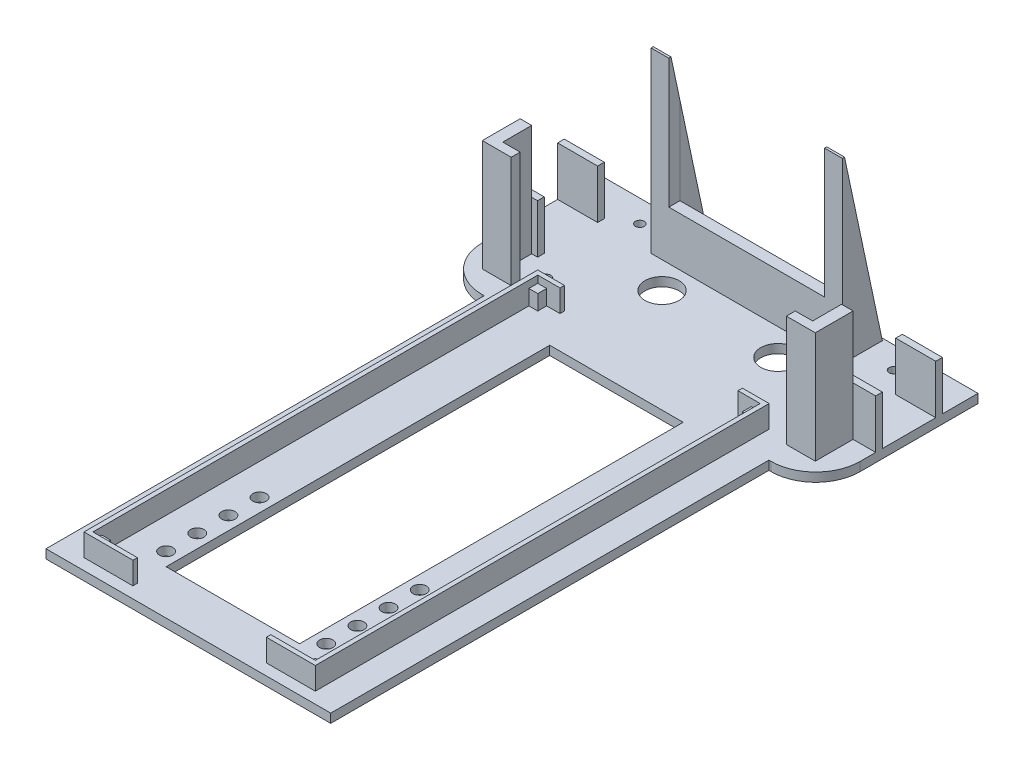
SolidWorks part; units mm, degrees
ref_plane "Front Plane" through (0, 0, 0) normal (0, 0, 1) x (1, 0, 0)
ref_plane "Top Plane" through (0, 0, 0) normal (0, 1, 0) x (1, 0, 0)
ref_plane "Right Plane" through (0, 0, 0) normal (1, 0, 0) x (0, 0, -1)
sketch "base" plane through (0, 0, 0) normal (0, 1, 0) x (1, 0, 0)
  line L1 (-42.5, 50) -> (42.5, 50)
  line L2 (-42.5, 50) -> (-42.5, -50)
  line L3 (-42.5, -50) -> (42.5, -50)
  line L4 (42.5, 50) -> (42.5, -50)
  line L5 (-42.5, 50) -> (42.5, -50) construction
  line L6 (-42.5, -50) -> (42.5, 50) construction
  point P0 (0, 0)
extrude "Boss-Extrude2" add sketch "base" along normal blind 2
sketch "Sketch3" plane through (0, 2, 0) normal (0, 1, 0) x (1, 0, 0)
  line L0 (42.5, 50) -> (-42.5, 50) construction
  line L9 (42.5, 40.5) -> (33.5, 40.5)
  line L10 (42.5, 40.5) -> (42.5, 42)
  line L11 (42.5, 42) -> (33.5, 42)
  line L12 (33.5, 40.5) -> (33.5, 42)
  line L13 (42.5, 28.5) -> (33.5, 28.5)
  line L14 (42.5, 28.5) -> (42.5, 27)
  line L15 (42.5, 27) -> (33.5, 27)
  line L16 (33.5, 28.5) -> (33.5, 27)
  line L17 (0, 50) -> (0, 24.8755)
  line L18 (-42.5, 42) -> (-33.5, 42)
  line L19 (-33.5, 40.5) -> (-33.5, 42)
  line L20 (-42.5, 40.5) -> (-33.5, 40.5)
  line L21 (-42.5, 40.5) -> (-42.5, 42)
  line L22 (-42.5, 27) -> (-33.5, 27)
  line L23 (-33.5, 28.5) -> (-33.5, 27)
  line L24 (-42.5, 28.5) -> (-33.5, 28.5)
  line L25 (-42.5, 28.5) -> (-42.5, 27)
  line L27 (-21.5, 40.5) -> (21.5, 40.5)
  line L28 (-21.5, 40.5) -> (-21.5, 43)
  line L29 (-21.5, 43) -> (21.5, 43)
  line L30 (21.5, 40.5) -> (21.5, 43)
  point P26 (21.5, 41.75)
  dimension "D1" = 9.5
  dimension "D2" = 9
  dimension "D3" = 12
  dimension "D4" = 12
  dimension "D5" = 12
  dimension "D7" = 8
  dimension "D8" = 7
  dimension "D9" = 9.5
  dimension "D11" = 1.5
extrude "Boss-Extrude4" add sketch "Sketch3" along normal blind 11 contours L18 L19 L20 L21 | L22 L23 L24 L25 | L28 L27 L30 L29 | L10 L9 L12 L11 | L14 L13 L16 L15
sketch "Sketch13" plane through (0, 2, 0) normal (0, 1, 0) x (1, 0, 0)
  line L0 (33.5, 40.5) -> (33.5, 42) construction
  line L1 (42.5, 42) -> (33.5, 42) construction
  line L2 (42.5, 28.5) -> (42.5, 40.5) construction
  line L3 (42.5, 34.5) -> (-42.5, 34.5)
  line L4 (-42.5, 40.5) -> (-42.5, 28.5) construction
  line L5 (-42.5, 34.5) -> (42.5, 34.5)
  line L6 (0, 50) -> (0, -50)
  line L7 (-42.5, -50) -> (42.5, -50) construction
  line L9 (-15, -50) -> (15, -50)
  line L10 (-15, -50) -> (-15, 11.2308)
  line L11 (-15, 11.2308) -> (15, 11.2308)
  line L12 (15, -50) -> (15, 11.2308)
  circle A0 centre (28.5, 45) radius 1
  circle A1 centre (28.5, 24) radius 1
  circle A2 centre (-28.5, 24) radius 1
  circle A3 centre (-28.5, 45) radius 1
  circle A4 centre (13.025, 34.5) radius 3.8478
  circle A5 centre (-13.025, 34.5) radius 3.8478
  line M29 (-42.5, -50) -> (42.5, -50)
  dimension "D1" = 2
  dimension "D4" = 30
  dimension "D2" = 5
  dimension "D3" = 3
  dimension "D5" = 15
extrude "Cut-Extrude2" cut sketch "Sketch13" against normal through all contours A5 L3 | A5 L3 | L3 A4 | L3 A4 | L11 L10 L6 M29 | L12 L11 L6 M29 | A0 | A1 | A2 | A3 region at (13.025, 2, -32.8669) region at (13.025, 2, -36.1331) region at (7.5, 2, 19.3846) region at (-7.5, 2, 19.3846) region at (-13.025, 2, -32.8669) region at (-13.025, 2, -36.1331)
sketch "Sketch14" plane through (0, 2, 0) normal (0, 1, 0) x (1, 0, 0)
  line L7 (42.5, 27) -> (33.5, 27) construction
  line L8 (34.8258, 20.5) -> (37.4214, 20.5)
  line L9 (34.8258, 20.5) -> (34.8258, 27)
  line L10 (34.8258, 27) -> (37.4214, 27)
  line L11 (37.4214, 20.5) -> (37.4214, 27)
  line L13 (37.4214, 20.5) -> (30.9214, 20.5)
  line L14 (37.4214, 20.5) -> (37.4214, 18.5)
  line L15 (37.4214, 18.5) -> (30.9214, 18.5)
  line L16 (30.9214, 20.5) -> (30.9214, 18.5)
  line L21 (0, 50) -> (0, -3.6791)
  line L30 (-37.4214, 18.5) -> (-30.9214, 18.5)
  line L31 (-30.9214, 20.5) -> (-30.9214, 18.5)
  line L32 (-37.4214, 20.5) -> (-30.9214, 20.5)
  line L33 (-37.4214, 20.5) -> (-37.4214, 18.5)
  line L34 (-34.8258, 27) -> (-37.4214, 27)
  line L35 (-37.4214, 20.5) -> (-37.4214, 27)
  line L36 (-34.8258, 20.5) -> (-37.4214, 20.5)
  line L37 (-34.8258, 20.5) -> (-34.8258, 27)
  line M34 (42.5, 27) -> (33.5, 27)
  line M50 (-33.5, 27) -> (-42.5, 27)
extrude "Boss-Extrude5" add sketch "Sketch14" along normal blind 25 contours L32 L37 L35 M50 | L32 L33 L30 L31 | L8 L11 L9 M34 | L13 L16 L15 L14 L8 region at (36.1236, 2, -23.75) region at (34.1714, 2, -19.5) region at (-34.1714, 2, -19.5) region at (-36.1236, 2, -23.75)
sketch "Sketch16" plane through (0, 13, 0) normal (0, 1, 0) x (1, 0, 0)
  line L0 (-21.5, 43) -> (21.5, 43) construction
  line L5 (21.5, 40.5) -> (17.5046, 40.5)
  line L6 (21.5, 40.5) -> (21.5, 43)
  line L7 (21.5, 43) -> (17.5046, 43)
  line L8 (17.5046, 40.5) -> (17.5046, 43)
  line L10 (0, 43) -> (0, 40.5)
  line L11 (-21.5, 43) -> (-17.5046, 43)
  line L12 (-17.5046, 40.5) -> (-17.5046, 43)
  line L13 (-21.5, 40.5) -> (-17.5046, 40.5)
  line L14 (-21.5, 40.5) -> (-21.5, 43)
  line M6 (21.5, 43) -> (-21.5, 43)
  line M7 (-21.5, 43) -> (-21.5, 40.5)
  line M8 (-21.5, 40.5) -> (21.5, 40.5)
  line M9 (21.5, 40.5) -> (21.5, 43)
extrude "Boss-Extrude6" add sketch "Sketch16" along normal blind 29 contours L12 M8 M6 M7 | L8 M8 M9 M6 region at (19.5023, 13, -41.75) region at (-19.5023, 13, -41.75)
sketch "Sketch18" plane through (0, 2, 0) normal (0, 1, 0) x (1, 0, 0)
  line L0 (0, 50) -> (0, 43)
  line L1 (21.5, 43) -> (17.5, 43)
  line L2 (21.5, 43) -> (21.5, 49.5)
  line L3 (21.5, 49.5) -> (17.5, 49.5)
  line L4 (17.5, 43) -> (17.5, 49.5)
  line L5 (0, 50) -> (0, 24.8755) construction
  line L6 (-21.5, 49.5) -> (-17.5, 49.5)
  line L7 (-17.5, 43) -> (-17.5, 49.5)
  line L8 (-21.5, 43) -> (-17.5, 43)
  line L9 (-21.5, 43) -> (-21.5, 49.5)
  line M40 (-21.5, 43) -> (21.5, 43)
extrude "Boss-Extrude7" add sketch "Sketch18" along normal blind 40 contours L9 L7 L6 M40 | L4 L2 L3 M40 region at (-19.5, 2, -46.25) region at (19.5, 2, -46.25)
chamfer "Chamfer1" distance 40 angle 12 2 edges at (-19.5, 42, -49.5) (19.5, 42, -49.5) first distance on face at (-19.5, 22, -49.5) first distance on face at (19.5, 22, -49.5)
sketch "Sketch19" plane through (0, 2, 0) normal (0, 1, 0) x (1, 0, 0)
  line L9 (42.5, -50) -> (42.5, 27) construction
  line L10 (-32, 13.5) -> (-42.5, 13.5)
  line L11 (-32, 13.5) -> (-32, -50)
  line L12 (-32, -50) -> (-42.5, -50)
  line L13 (-42.5, 13.5) -> (-42.5, -50)
  line L14 (32, -50) -> (42.5, -50)
  line L15 (42.5, 13.5) -> (42.5, -50)
  line L16 (32, 13.5) -> (42.5, 13.5)
  line L17 (32, 13.5) -> (32, -50)
  line L18 (-42.5, -50) -> (-15, -50) construction
  line L19 (-21.0587, -50) -> (18.5573, -50)
  line L20 (-21.0587, -50) -> (-21.0587, 13.5)
  line L21 (-21.0587, 13.5) -> (18.5573, 13.5)
  line L22 (18.5573, -50) -> (18.5573, 13.5)
  line M20 (-42.5, 27) -> (-42.5, -50)
  line M21 (-42.5, -50) -> (-15, -50)
  line M22 (42.5, -50) -> (42.5, 27)
  dimension "D1" = 10.5
  dimension "D2" = 10.5
  dimension "D3" = 0
extrude "Cut-Extrude3" cut sketch "Sketch19" against normal through all contours L11 L10 M20 M21 | L16 L17 M21 M22 region at (-37.25, 2, 18.25) region at (37.25, 2, 18.25)
sketch "Sketch20" plane through (0, 2, 0) normal (0, 1, 0) x (1, 0, 0)
  line L5 (-25, -50) -> (-26, -50)
  line L6 (-25, -50) -> (-25, 19.5389)
  line L7 (-25, 19.5389) -> (-26, 19.5389)
  line L8 (-26, -50) -> (-26, 19.5389)
  line L13 (-25, 18.5389) -> (-20, 18.5389)
  line L14 (-25, 18.5389) -> (-25, 19.5389)
  line L15 (-25, 19.5389) -> (-20, 19.5389)
  line L16 (-20, 18.5389) -> (-20, 19.5389)
  line L17 (25, 19.5389) -> (20, 19.5389)
  line L18 (20, 18.5389) -> (20, 19.5389)
  line L19 (25, 18.5389) -> (20, 18.5389)
  line L20 (25, 18.5389) -> (25, 19.5389)
  line L21 (25, 19.5389) -> (26, 19.5389)
  line L22 (26, -50) -> (26, 19.5389)
  line L23 (25, -50) -> (26, -50)
  line L24 (25, -50) -> (25, 19.5389)
extrude "Boss-Extrude8" add sketch "Sketch20" along normal blind 5 contours L8 L6 L7 | L24 L22 L21 L20 | L15 L16 L13 L14 | L20 L19 L18 L17 region at (-25.5, 2, 15.2306) region at (25.5, 2, 15.2306)
fillet "Fillet1" radius 10 2 edges at (42.5, 1, -13.5) (-42.5, 1, -13.5)
sketch "Sketch21" plane through (0, 2, 0) normal (0, 1, 0) x (1, 0, 0)
  line L1 (-25, 18.5389) -> (-23, 18.5389)
  line L2 (-25, 18.5389) -> (-25, 16.5389)
  line L3 (-25, 16.5389) -> (-23, 16.5389)
  line L4 (-23, 18.5389) -> (-23, 16.5389)
  line L5 (25, 18.5389) -> (23, 18.5389)
  line L6 (25, 18.5389) -> (25, 16.5389)
  line L7 (25, 16.5389) -> (23, 16.5389)
  line L8 (23, 18.5389) -> (23, 16.5389)
extrude "Boss-Extrude9" add sketch "Sketch21" along normal blind 3.4
sketch "Sketch22" plane through (0, 0, 50) normal (0, 0, 1) x (1, 0, 0)
  line L0 (32, 0) -> (32, 2) construction
  line L1 (-32, 2) -> (32, 2)
  line L2 (-32, 2) -> (-32, 0)
  line L3 (-32, 0) -> (32, 0)
  line L4 (32, 2) -> (32, 0)
  point P6 (42.5, 0)
  dimension "D1" = 0
extrude "Boss-Extrude10" add sketch "Sketch22" along normal blind 35
sketch "Sketch23" plane through (0, 2, 0) normal (0, 1, 0) x (1, 0, 0)
  line L0 (0, 50) -> (0, 24.8755) construction
  line L1 (32, -85) -> (-32, -85) construction
  line L2 (0, -85) -> (0, -60.7258)
  line L4 (-15, -75) -> (15, -75)
  line L5 (-15, -75) -> (-15, -47.5134)
  line L6 (-15, -47.5134) -> (15, -47.5134)
  line L7 (15, -75) -> (15, -47.5134)
  circle A0 centre (18, -72) radius 1.5
  circle A1 centre (18, -65) radius 1.5
  circle A2 centre (18, -58) radius 1.5
  circle A3 centre (18, -51) radius 1.5
  circle A4 centre (-18, -51) radius 1.5
  circle A5 centre (-18, -58) radius 1.5
  circle A6 centre (-18, -65) radius 1.5
  circle A7 centre (-18, -72) radius 1.5
  dimension "D2" = 3
  dimension "D1" = 18
  dimension "D3" = 13
  dimension "D5" = 30
  dimension "D6" = 15
  dimension "D7" = 10
  dimension "D4" = 4
extrude "Cut-Extrude4" cut sketch "Sketch23" against normal through all contours A0 | A1 | A2 | A3 | A7 | A6 | A5 | A4 | L5 L6 L7 L4
sketch "Sketch24" plane through (0, 2, 0) normal (0, 1, 0) x (1, 0, 0)
  line L0 (-15, -75) -> (-15, 11.2308) construction
  line L1 (-26, -50) -> (-25, -50)
  line L2 (-26, -50) -> (-26, -82.46)
  line L3 (-26, -82.46) -> (-25, -82.46)
  line L4 (-25, -50) -> (-25, -82.46)
  line L5 (-25, -82.46) -> (-15, -82.46)
  line L6 (-25, -82.46) -> (-25, -81.46)
  line L7 (-25, -81.46) -> (-15, -81.46)
  line L8 (-15, -82.46) -> (-15, -81.46)
  line L12 (0, 50) -> (0, -73.0677)
  line L13 (25, -81.46) -> (15, -81.46)
  line L14 (15, -82.46) -> (15, -81.46)
  line L15 (25, -82.46) -> (15, -82.46)
  line L16 (25, -82.46) -> (25, -81.46)
  line L17 (26, -82.46) -> (25, -82.46)
  line L18 (25, -50) -> (25, -82.46)
  line L19 (26, -50) -> (25, -50)
  line L20 (26, -50) -> (26, -82.46)
  dimension "D1" = 1
  dimension "D2" = 32.46
  dimension "D3" = 1
extrude "Boss-Extrude11" add sketch "Sketch24" along normal blind 5 contours L4 L1 L2 L3 | L5 L8 L7 L4 | L18 L19 L20 L17 | L16 L13 L14 L15 region at (-25.5, 2, 66.23) region at (-20, 2, 81.96)
sketch "Sketch25" plane through (0, 2, 0) normal (0, 1, 0) x (1, 0, 0)
  line L0 (0, 50) -> (0, -75.5417)
sketch "Sketch26" plane through (0, 2, 0) normal (0, 1, 0) x (1, 0, 0)
  line L0 (0, -75) -> (0, -83.8712)
  line L1 (-25, -81.46) -> (-23, -81.46)
  line L2 (-25, -81.46) -> (-25, -79.46)
  line L3 (-25, -79.46) -> (-23, -79.46)
  line L4 (-23, -81.46) -> (-23, -79.46)
  line L5 (-15, -75) -> (15, -75) construction
  line L6 (25, -79.46) -> (23, -79.46)
  line L7 (23, -81.46) -> (23, -79.46)
  line L8 (25, -81.46) -> (23, -81.46)
  line L9 (25, -81.46) -> (25, -79.46)
extrude "Boss-Extrude13" add sketch "Sketch26" along normal blind 3.4 contours L8 L9 L6 L7 | L4 L3 L2 L1 region at (24, 2, 80.46)
